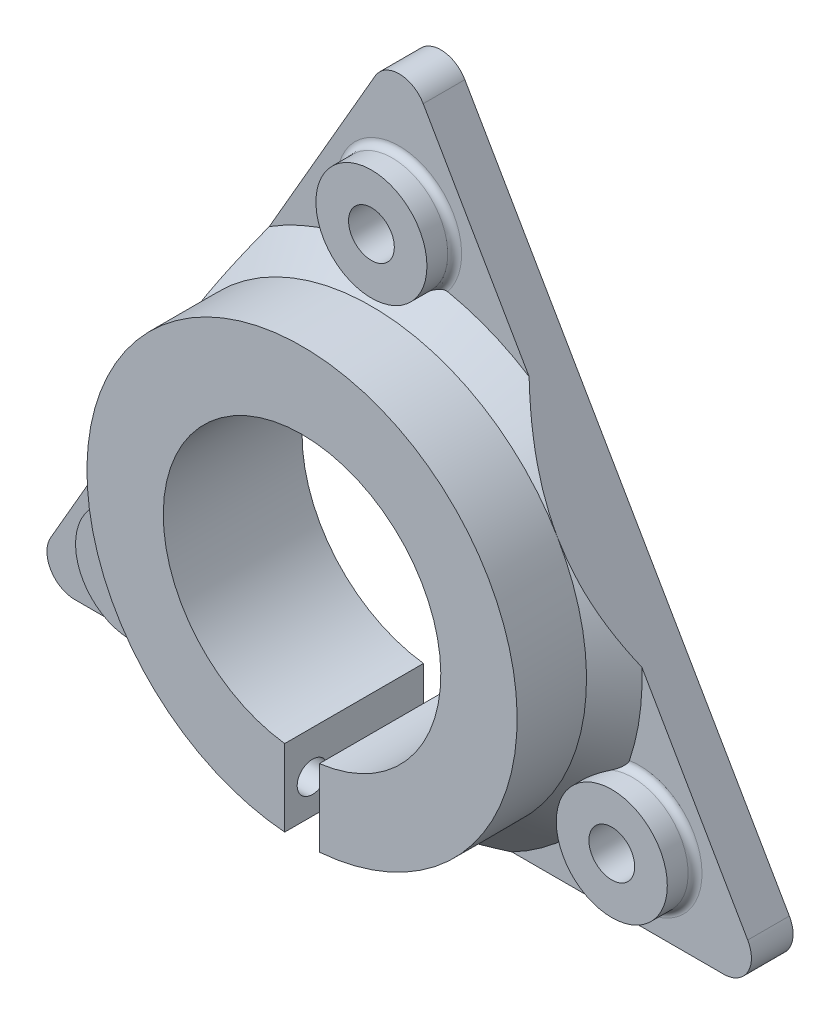
SolidWorks part; units mm, degrees
ref_plane "前视基准面" through (0, 0, 0) normal (0, 0, 1) x (1, 0, 0)
ref_plane "上视基准面" through (0, 0, 0) normal (0, 1, 0) x (1, 0, 0)
ref_plane "右视基准面" through (0, 0, 0) normal (1, 0, 0) x (0, 0, -1)
sketch "草图1" plane through (0, 0, 0) normal (0, 0, 1) x (1, 0, 0)
  line L1 (0, 20) -> (-17.3205, -10) construction
  line L2 (-17.3205, -10) -> (17.3205, -10) construction
  line L3 (17.3205, -10) -> (0, 20) construction
  line L4 (0, 31) -> (-26.8468, -15.5)
  line L5 (-26.8468, -15.5) -> (26.8468, -15.5)
  line L6 (26.8468, -15.5) -> (0, 31)
  circle A0 centre (0, 0) radius 10 construction
  circle A1 centre (0, 20) radius 1.65
  circle A2 centre (17.3205, -10) radius 1.65
  circle A3 centre (-17.3205, -10) radius 1.65
  circle A4 centre (0, 0) radius 9
  circle A5 centre (0, 0) radius 15.5 construction
  dimension "D2" = 3.3
  dimension "D3" = 3.3
  dimension "D4" = 3.3
  dimension "D5" = 18
  dimension "D1" = 20
  dimension "D6" = 31
extrude "凸台-拉伸1" add sketch "草图1" along normal blind 3
sketch "草图2" plane through (0, 0, 3) normal (0, 0, 1) x (1, 0, 0)
  line L0 (0, 31) -> (-26.8468, -15.5) construction
  circle A0 centre (0, 0) radius 9
  circle A1 centre (0, 0) radius 15.5
  dimension "D1" = 18
extrude "凸台-拉伸2" add sketch "草图2" along normal blind 7
sketch "草图3" plane through (0, 0, 10) normal (0, 0, 1) x (1, 0, 0)
  line L1 (1.25, -19) -> (-1.25, -19)
  line L2 (1.25, -19) -> (1.25, 1)
  line L3 (1.25, 1) -> (-1.25, 1)
  line L4 (-1.25, -19) -> (-1.25, 1)
  line L5 (1.25, -19) -> (-1.25, 1) construction
  line L6 (1.25, 1) -> (-1.25, -19) construction
  circle A0 centre (0, 0) radius 9 construction
  point P0 (0, -9)
  dimension "D1" = 20
  dimension "D2" = 2.5
extrude "切除-拉伸1" cut sketch "草图3" against normal blind 28
sketch "草图4" plane through (-1.25, 0, 0) normal (1, 0, 0) x (0, 0, -1)
  line L0 (0, -15.5) -> (0, 31) construction
  circle A1 centre (-8, -13) radius 1.1
  dimension "D1" = 8
  dimension "D2" = 13
  dimension "D3" = 2.2
extrude "切除-拉伸2" cut sketch "草图4" against normal through all both and the other way through all
sketch "草图5" plane through (0, 0, 10) normal (0, 0, 1) x (1, 0, 0)
  circle A0 centre (0, 0) radius 10
  dimension "D1" = 20
extrude "切除-拉伸3" cut sketch "草图5" against normal through all
ref_plane "基准面1" through (18.75, 0, 0) normal (1, 0, 0) x (0, 0, -1)
sketch "草图6" plane through (18.75, 0, 0) normal (1, 0, 0) x (0, 0, -1)
  circle A0 centre (-8, -13) radius 1.9
  dimension "D1" = 3.8
extrude "切除-拉伸8" cut sketch "草图6" against normal blind 13
mirror "镜向1" about plane through (0, 0, 0) normal (1, 0, 0) of "切除-拉伸8"
chamfer "倒角1" distance 2 angle 45 1 edges at (-13.7252, -7.202, 3)
fillet "圆角2" radius 2 3 edges at (0, 31, 1.5) (26.8468, -15.5, 1.5) (-26.8468, -15.5, 1.5)
sketch "草图7" plane through (0, 0, 3) normal (0, 0, 1) x (1, 0, 0)
  circle A0 centre (0, 20) radius 1.65
  circle A1 centre (0, 20) radius 4
  circle A2 centre (-17.3205, -10) radius 1.65
  circle A3 centre (17.3205, -10) radius 1.65
  circle A4 centre (17.3205, -10) radius 4
  circle A5 centre (-17.3205, -10) radius 4
  dimension "D1" = 8
  dimension "D2" = 3.3
  dimension "D3" = 3.3
  dimension "D4" = 8
  dimension "D5" = 8
extrude "凸台-拉伸3" add sketch "草图7" along normal blind 2
fillet "圆角3" radius 0.5 3 edges at (-20.7846, -12, 3) (20.7846, -12, 3) (0, 24, 3)
